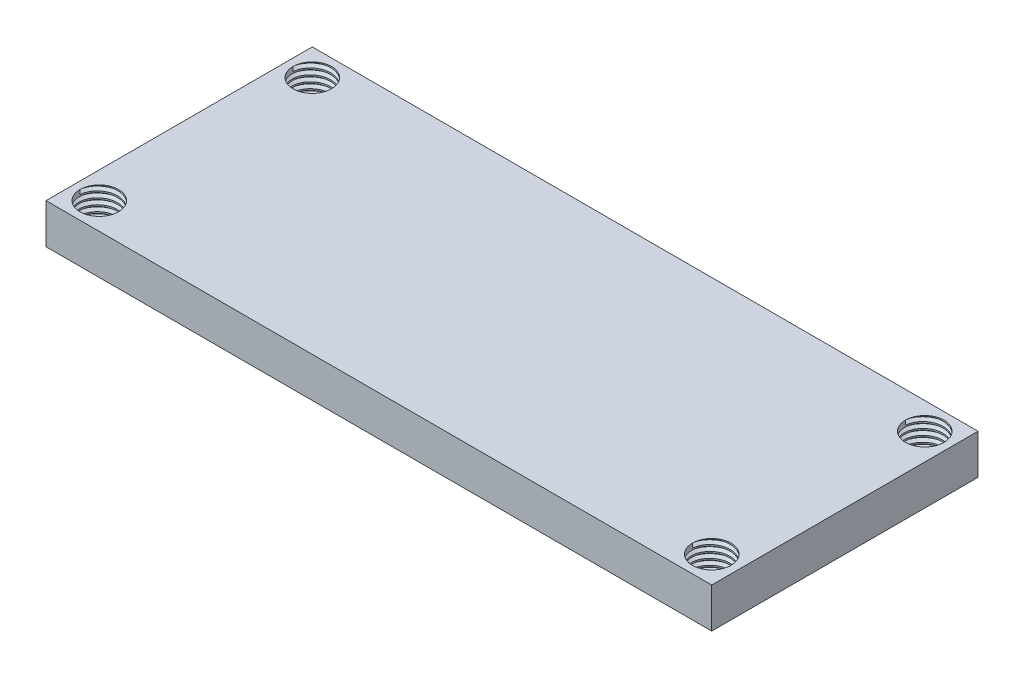
SolidWorks part; units mm, degrees
ref_plane "Front Plane" through (0, 0, 0) normal (0, 0, 1) x (1, 0, 0)
ref_plane "Top Plane" through (0, 0, 0) normal (0, 1, 0) x (1, 0, 0)
ref_plane "Right Plane" through (0, 0, 0) normal (1, 0, 0) x (0, 0, -1)
sketch "Sketch1" plane through (0, 0, 0) normal (0, 1, 0) x (1, 0, 0)
  line L1 (-20.9859, 11.4085) -> (29.0141, 11.4085)
  line L2 (-20.9859, 11.4085) -> (-20.9859, -8.5915)
  line L3 (-20.9859, -8.5915) -> (29.0141, -8.5915)
  line L4 (29.0141, 11.4085) -> (29.0141, -8.5915)
  dimension "D1" = 20
  dimension "D2" = 50
extrude "Boss-Extrude1" add sketch "Sketch1" along normal blind 3
sketch "Sketch2" plane through (0, 3, 0) normal (0, 1, 0) x (1, 0, 0)
  line L0 (29.0141, 11.4085) -> (-20.9859, 11.4085) construction
  line L1 (29.0141, -8.5915) -> (29.0141, 11.4085) construction
  line L2 (-20.9859, -8.5915) -> (29.0141, -8.5915) construction
  line L3 (-20.9859, 11.4085) -> (-20.9859, -8.5915) construction
  circle A0 centre (-18.9859, -6.5915) radius 1.25
  circle A1 centre (-18.9859, 9.4085) radius 1.25
  circle A2 centre (27.0141, -6.5915) radius 1.25
  circle A3 centre (27.0141, 9.4085) radius 1.25
  point P18 (-20.4002, -8.5915)
  dimension "D1" = 2.5
  dimension "D2" = 2.5
  dimension "D3" = 2.5
  dimension "D4" = 2.5
  dimension "D5" = 2
  dimension "D6" = 2
  dimension "D7" = 2
  dimension "D8" = 2
  dimension "D9" = 2
  dimension "D10" = 2
  dimension "D11" = 2
  dimension "D12" = 2
  dimension "D13" = 2
hole_wizard "M2.5 Clearance Hole1" positions "Sketch3" profile "Sketch4" hole size "M2.5" standard "ANSI Metric"
sketch "Sketch3" plane through (0, 3, 0) normal (0, 1, 0) x (1, 0, 0)
  point P0 (-18.9859, -6.5915)
  point P3 (-18.9859, 9.4085)
  point P6 (27.0141, -6.5915)
  point P9 (27.0141, 9.4085)
sketch "Sketch4" plane through (-18.9859, 3, 6.5915) normal (1, 0, 0) x (0, 0, 1)
  line L0 (0, 0) -> (0, 3.8712)
  line L1 (0, 3.8712) -> (1.45, 3)
  line L2 (1.45, 3) -> (1.45, 0)
  line L5 (1.45, 0) -> (0, 0)
  line L10 (0, 3.8712) -> (-1.45, 3) construction
  line L11 (0, -6.35) -> (0, 107.95) construction
  dimension "Hole Dia." = 2.9
  dimension "Hole Depth" = 3
  dimension "Drill Angle" = 118
thread "Thread1" pitch 0.45 method cut profile "Thread Profile1" start angle 0, offset 0, length 3, pitch 0.45, diameter 2.9
ref_plane "Plane1" through (-20.4359, 3, 6.5915) normal (0, 0, 1) x (-1, 0, 0)
sketch "Thread Profile1" plane through (-20.4359, 3, 6.5915) normal (0, 0, 1) x (-1, 0, 0)
  line L0 (0, 0) -> (0, 0.45) construction
  line L1 (0, 0) -> (0.2436, 0.1406)
  line L2 (0.2436, 0.1406) -> (0.2436, 0.1969)
  line L3 (0.2436, 0.1969) -> (0, 0.3375)
  line L4 (0.2436, 0.1687) -> (0, 0.1687) construction
  line L11 (0, 0) -> (0, 0.3375)
  point P2 (0, 0)
  dimension "Pitch" = 0.45
  dimension "Profile_Angle" = 60
  dimension "Profile_Land" = 0.0562
  dimension "Profile_Height" = 0.2436
thread "Thread2" pitch 0.45 method cut profile "Thread Profile2" start angle 0, offset 0, length 3, pitch 0.45, diameter 2.9
ref_plane "Plane2" through (-20.4359, 3, -9.4085) normal (0, 0, 1) x (-1, 0, 0)
sketch "Thread Profile2" plane through (-20.4359, 3, -9.4085) normal (0, 0, 1) x (-1, 0, 0)
  line L0 (0, 0) -> (0, 0.45) construction
  line L1 (0, 0) -> (0.2436, 0.1406)
  line L2 (0.2436, 0.1406) -> (0.2436, 0.1969)
  line L3 (0.2436, 0.1969) -> (0, 0.3375)
  line L4 (0.2436, 0.1687) -> (0, 0.1687) construction
  line L11 (0, 0) -> (0, 0.3375)
  point P2 (0, 0)
  dimension "Pitch" = 0.45
  dimension "Profile_Angle" = 60
  dimension "Profile_Land" = 0.0562
  dimension "Profile_Height" = 0.2436
thread "Thread3" pitch 0.45 method cut profile "Thread Profile3" start angle 0, offset 0, length 3, pitch 0.45, diameter 2.9
ref_plane "Plane3" through (25.5641, 3, 6.5915) normal (0, 0, 1) x (-1, 0, 0)
sketch "Thread Profile3" plane through (25.5641, 3, 6.5915) normal (0, 0, 1) x (-1, 0, 0)
  line L0 (0, 0) -> (0, 0.45) construction
  line L1 (0, 0) -> (0.2436, 0.1406)
  line L2 (0.2436, 0.1406) -> (0.2436, 0.1969)
  line L3 (0.2436, 0.1969) -> (0, 0.3375)
  line L4 (0.2436, 0.1687) -> (0, 0.1687) construction
  line L11 (0, 0) -> (0, 0.3375)
  point P2 (0, 0)
  dimension "Pitch" = 0.45
  dimension "Profile_Angle" = 60
  dimension "Profile_Land" = 0.0562
  dimension "Profile_Height" = 0.2436
thread "Thread4" pitch 0.45 method cut profile "Thread Profile4" start angle 0, offset 0, length 3, pitch 0.45, diameter 2.9
ref_plane "Plane4" through (25.5641, 3, -9.4085) normal (0, 0, 1) x (-1, 0, 0)
sketch "Thread Profile4" plane through (25.5641, 3, -9.4085) normal (0, 0, 1) x (-1, 0, 0)
  line L0 (0, 0) -> (0, 0.45) construction
  line L1 (0, 0) -> (0.2436, 0.1406)
  line L2 (0.2436, 0.1406) -> (0.2436, 0.1969)
  line L3 (0.2436, 0.1969) -> (0, 0.3375)
  line L4 (0.2436, 0.1687) -> (0, 0.1687) construction
  line L11 (0, 0) -> (0, 0.3375)
  point P2 (0, 0)
  dimension "Pitch" = 0.45
  dimension "Profile_Angle" = 60
  dimension "Profile_Land" = 0.0562
  dimension "Profile_Height" = 0.2436
